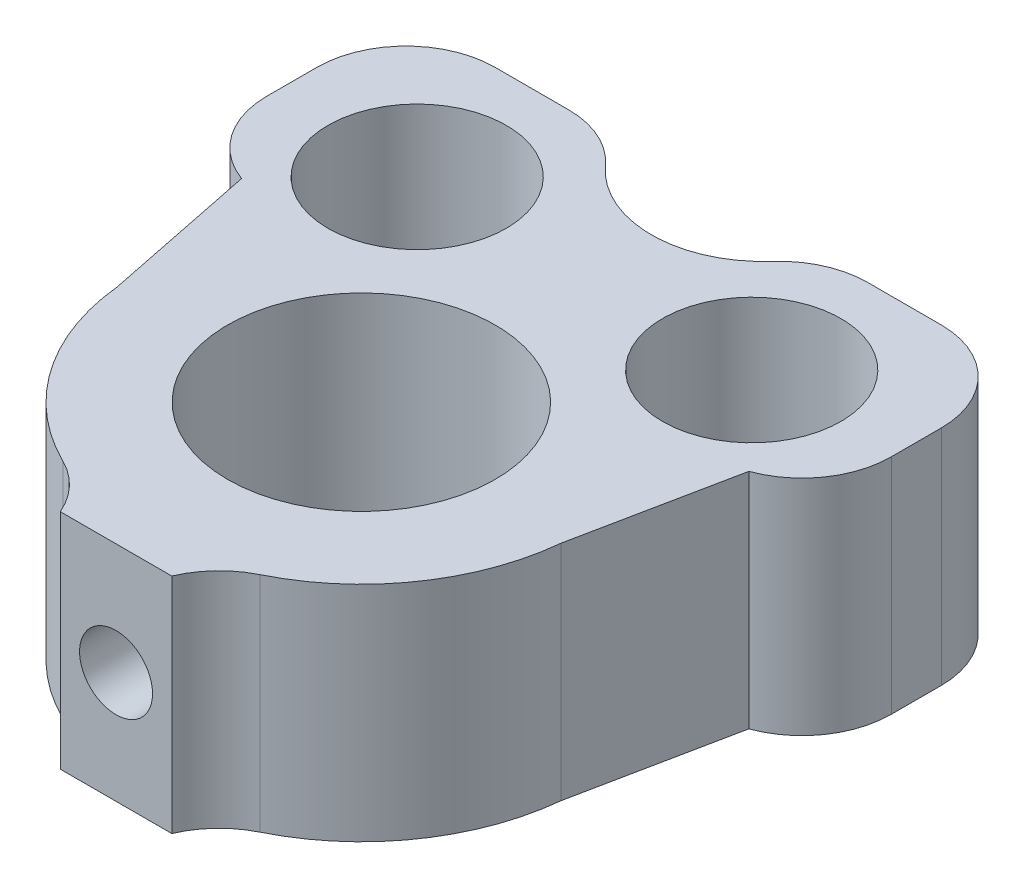
SolidWorks part; units mm, degrees
ref_plane "Alzado" through (0, 0, 0) normal (0, 0, 1) x (1, 0, 0)
ref_plane "Planta" through (0, 0, 0) normal (0, 1, 0) x (1, 0, 0)
ref_plane "Vista lateral" through (0, 0, 0) normal (1, 0, 0) x (0, 0, -1)
sketch "Croquis1" plane through (0, 0, 0) normal (0, 1, 0) x (1, 0, 0)
  line L0 (-14, 16) -> (-4.5826, 16)
  line L1 (-14, 16) -> (14, 16) construction
  line L2 (-14, 16) -> (-14, 6)
  line L3 (-14, 6) -> (14, 6)
  line L4 (14, 16) -> (14, 6)
  line L5 (4.5826, 16) -> (14, 16)
  circle A0 centre (0, 0) radius 6
  circle A1 centre (0, 0) radius 10
  arc A2 (-4.5826, 16) -> (4.5826, 16) centre (0, 18) ccw
  point P8 (0, 6)
  point P13 (0, 16)
  dimension "D1" = 12
  dimension "D2" = 4
  dimension "D5" = 5
  dimension "D3" = 28
  dimension "D4" = 10
  dimension "D6" = 2
extrude "Saliente-Extruir1" add sketch "Croquis1" along normal blind 10 contours A1 L3 L4 L1 L2 | L3 A1 | L3 A1 A0 region at (0, 0, -11.3533) region at (0, 0, -7.6311) region at (-4, 0, -5.7439)
sketch "Croquis2" plane through (0, 10, 0) normal (0, 1, 0) x (1, 0, 0)
  line L0 (-7.5, 10) -> (7.5, 10) construction
  circle A0 centre (-7.5, 10) radius 4
  circle A1 centre (7.5, 10) radius 4
  point P4 (0, 10)
  dimension "D1" = 8
  dimension "D2" = 15
  dimension "D3" = 10
extrude "Cortar-Extruir1" cut sketch "Croquis2" against normal blind 10
chamfer "Chaflán1" distance 10 angle 45 2 edges at (-8, 5, -6) (8, 5, -6) first distance on face at (0, 5, 2)
sketch "Croquis3" plane through (0, 0, 0) normal (0, 1, 0) x (1, 0, 0)
  line L1 (-2.5, -9) -> (2.5, -9)
  line L2 (-2.5, -9) -> (-2.5, -11)
  line L3 (-2.5, -11) -> (2.5, -11)
  line L4 (2.5, -9) -> (2.5, -11)
  line L5 (-2.5, -9) -> (2.5, -11) construction
  line L6 (-2.5, -11) -> (2.5, -9) construction
  arc A0 (-9.9499, -1) -> (9.9499, -1) centre (0, 0) ccw construction
  point P0 (0, -10)
  dimension "D1" = 5
  dimension "D2" = 2
extrude "Saliente-Extruir2" add sketch "Croquis3" along normal up to surface (10 mm away) up to face at (7.5, 10, -6)
sketch "Croquis4" plane through (0, 0, 11) normal (0, 0, 1) x (1, 0, 0)
  line L0 (2.5, 10) -> (2.5, 0) construction
  circle A0 centre (0, 5) radius 1.6351
  point P6 (2.5, 5)
  dimension "D1" = 3.2703
extrude "Cortar-Extruir2" cut sketch "Croquis4" against normal blind 10
fillet "Redondeo2" radius 4 8 edges at (14, 5, -16) (14, 5, -6) (-14, 5, -6) (-14, 5, -16) (-2.5, 5, 9.6825) (2.5, 5, 9.6825) (4.5826, 5, -16) (-4.5826, 5, -16)
